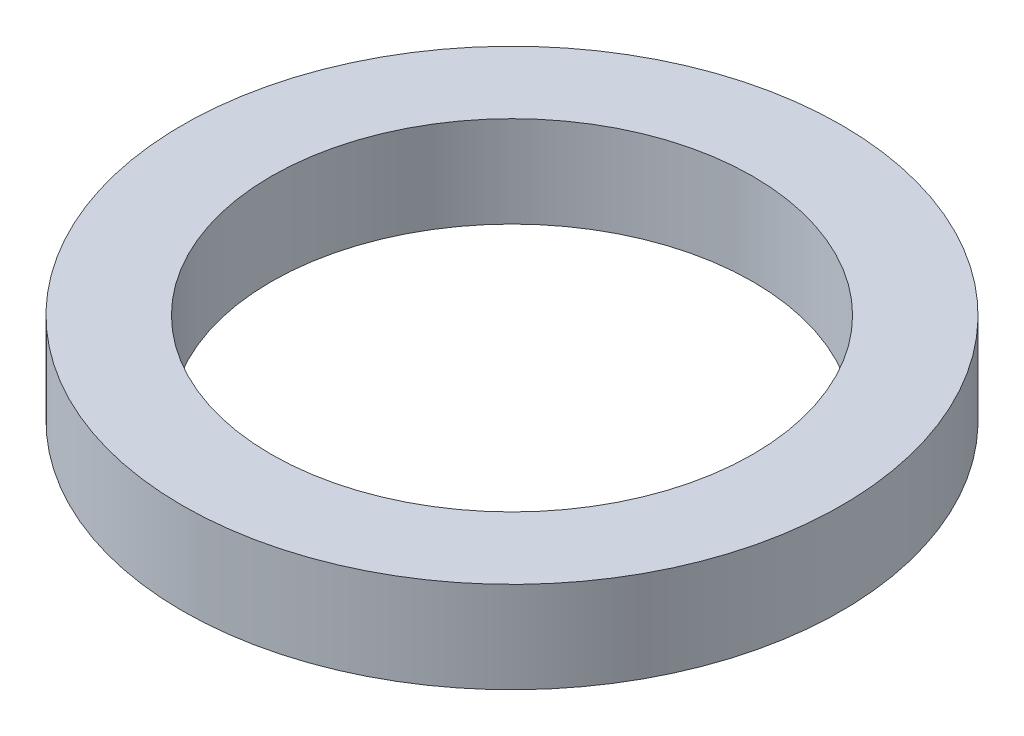
SolidWorks part; units mm, degrees
ref_plane "Front Plane" through (0, 0, 0) normal (0, 0, 1) x (1, 0, 0)
ref_plane "Top Plane" through (0, 0, 0) normal (0, 1, 0) x (1, 0, 0)
ref_plane "Right Plane" through (0, 0, 0) normal (1, 0, 0) x (0, 0, -1)
sketch "Sketch1" plane through (0, 0, 0) normal (0, 1, 0) x (1, 0, 0)
  circle A0 centre (0, 0) radius 65
  dimension "FLANGE_OD" = 130
extrude "Boss-Extrude1" add sketch "Sketch1" along normal blind 18
sketch "Sketch2" plane through (0, 0, 0) normal (0, 1, 0) x (1, 0, 0)
  circle A0 centre (0, 0) radius 47.5
  dimension "BORE_D" = 95
extrude "Cut-Extrude1" cut sketch "Sketch2" along normal through all
sketch "Sketch3" plane through (0, 18, 0) normal (0, 1, 0) x (1, 0, 0)
  circle A0 centre (0, 0) radius 30.1842 construction
  circle A1 centre (-30.1842, 0) radius 1.6183
  dimension "BOLT_D" = 3.2365
  dimension "BOLT_PCD" = 60.3683
extrude "Cut-Extrude2" cut sketch "Sketch3" against normal blind 13.0577 rebuild error yes
pattern_circular "CirPattern1" count 4 over 360 rebuild error yes
